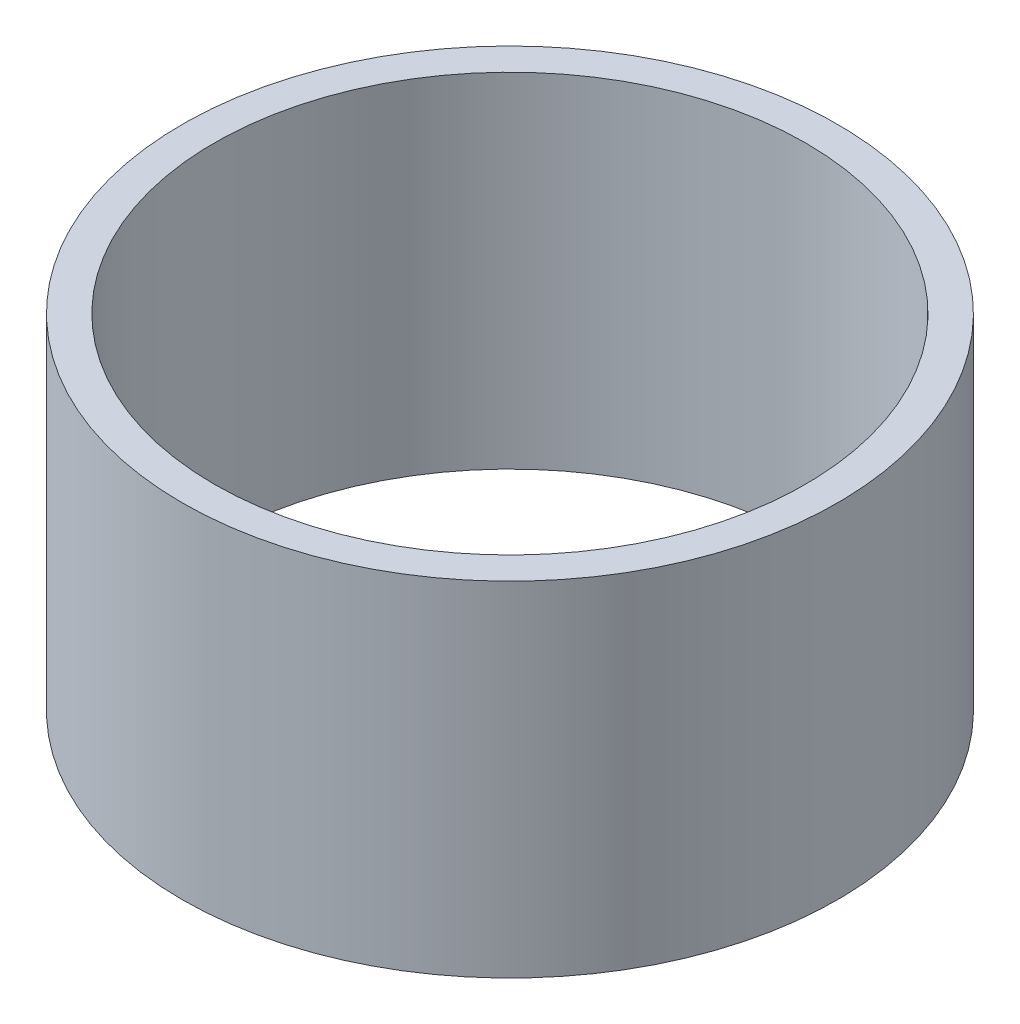
SolidWorks part; units mm, degrees
ref_plane "Front Plane" through (0, 0, 0) normal (0, 0, 1) x (1, 0, 0)
ref_plane "Top Plane" through (0, 0, 0) normal (0, 1, 0) x (1, 0, 0)
ref_plane "Right Plane" through (0, 0, 0) normal (1, 0, 0) x (0, 0, -1)
sketch "Sketch1" plane through (0, 0, 0) normal (0, 1, 0) x (1, 0, 0)
  circle A0 centre (0, 0) radius 47.5
  dimension "SLEEVE_OD" = 95
extrude "Boss-Extrude1" add sketch "Sketch1" along normal blind 49.8131
sketch "Sketch2" plane through (0, 0, 0) normal (0, 1, 0) x (1, 0, 0)
  circle A0 centre (0, 0) radius 42.8483
  dimension "BORE_D" = 85.6966
extrude "Cut-Extrude1" cut sketch "Sketch2" along normal through all
chamfer "Chamfer1" distance 3.0424 angle 45 rebuild error yes
